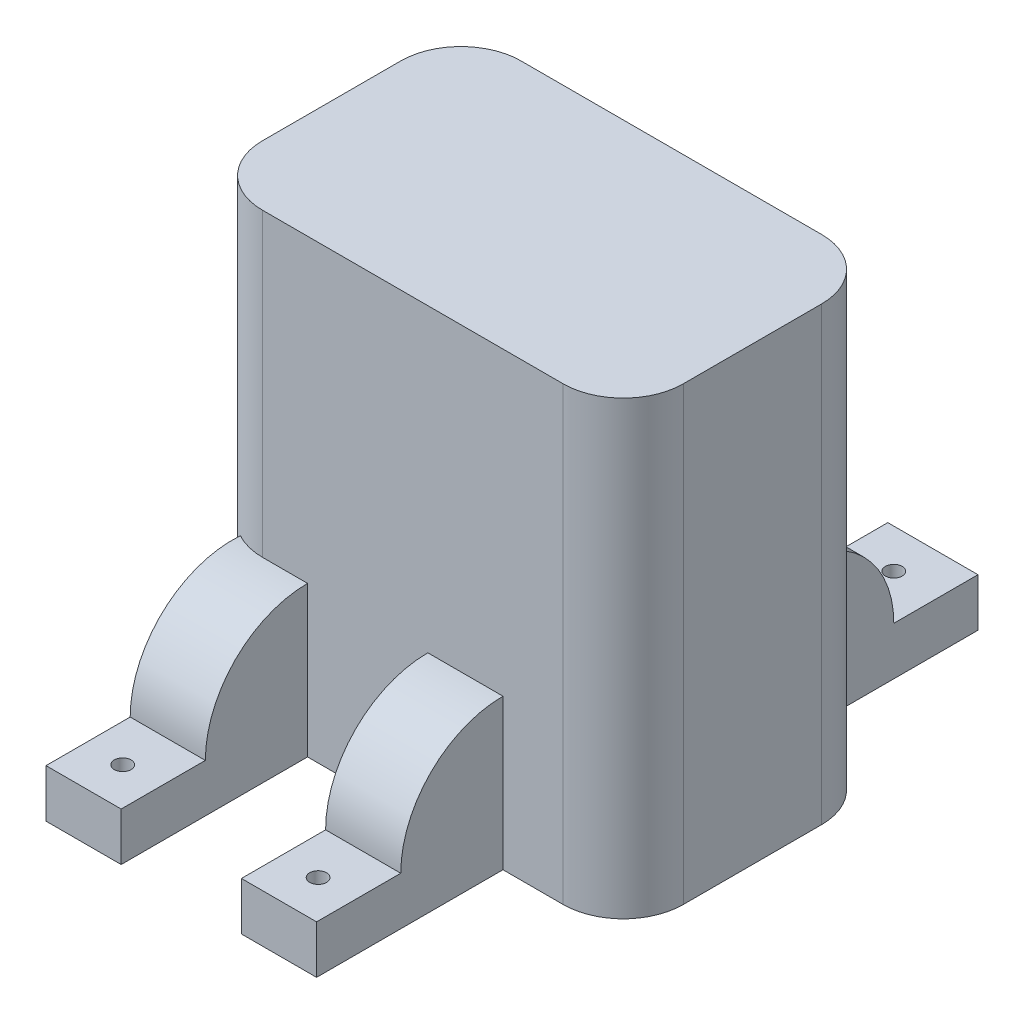
SolidWorks part; units mm, degrees
ref_plane "Plan de face" through (0, 0, 0) normal (0, 0, 1) x (1, 0, 0)
ref_plane "Plan de dessus" through (0, 0, 0) normal (0, 1, 0) x (1, 0, 0)
ref_plane "Plan de droite" through (0, 0, 0) normal (1, 0, 0) x (0, 0, -1)
sketch "Esquisse1" plane through (0, 0, 0) normal (0, 1, 0) x (1, 0, 0)
  line L1 (0, 0) -> (7, 0)
  line L2 (0, 0) -> (0, 4.3)
  line L3 (0, 4.3) -> (7, 4.3)
  line L4 (7, 0) -> (7, 4.3)
  dimension "D1" = 7
  dimension "D2" = 4.3
extrude "Boss.-Extru.1" add sketch "Esquisse1" along normal blind 7.5
shell "Coque1" thickness 1 removed face at (3.5, 0, -2.15)
sketch "Esquisse2" plane through (0, 0, 0) normal (0, 0, 1) x (1, 0, 0)
  line L0 (7, 0) -> (5, 0)
  line L1 (0, 0) -> (7, 0) construction
  line L2 (5, 0) -> (3.75, 0)
  line L3 (3.75, 0) -> (1.75, 0)
  line L4 (1.75, 0) -> (0.5, 0)
  line L5 (0.5, 0) -> (0, 0)
  line L7 (0.5, 0) -> (1.75, 0)
  line L8 (0.5, 0) -> (0.5, 0.8)
  line L9 (0.5, 0.8) -> (1.75, 0.8)
  line L10 (1.75, 0) -> (1.75, 0.8)
  line L11 (3.75, 0) -> (5, 0)
  line L12 (3.75, 0) -> (3.75, 0.8)
  line L13 (3.75, 0.8) -> (5, 0.8)
  line L14 (5, 0) -> (5, 0.8)
  dimension "D1" = 0.5
  dimension "D2" = 2
  dimension "D3" = 2
  dimension "D4" = 0.8
extrude "Boss.-Extru.2" add sketch "Esquisse2" along normal blind 3.1 from surface contours L8 L7 L10 L9 | L12 L11 L14 L13 starting at face at (3.5, 3.75, 0)
sketch "Esquisse3" plane through (0, 0, -4.3) normal (0, 0, -1) x (-1, 0, 0)
  line L0 (-7, 0) -> (-5.5, 0)
  line L1 (-7, 0) -> (0, 0) construction
  line L2 (0, 0) -> (-4, 0)
  line L4 (-5.5, 0) -> (-4, 0)
  line L5 (-5.5, 0) -> (-5.5, 0.8)
  line L6 (-5.5, 0.8) -> (-4, 0.8)
  line L7 (-4, 0) -> (-4, 0.8)
  dimension "D1" = 1.5
  dimension "D2" = 4
  dimension "D3" = 0.8
extrude "Boss.-Extru.3" add sketch "Esquisse3" along normal blind 3.1 from surface contours L5 L4 L7 L6 starting at face at (3.5, 3.75, -4.3)
sketch "Esquisse4" plane through (0, 0.8, 0) normal (0, 1, 0) x (1, 0, 0)
  line L0 (7, 4.3) -> (0, 4.3) construction
  line L3 (5.5, 7.4) -> (5.5, 4.3) construction
  line L4 (0, 0) -> (7, 0) construction
  line L5 (3.75, -3.1) -> (5, -3.1) construction
  line L8 (0.5, -3.1) -> (1.75, -3.1) construction
  circle A0 centre (4.75, 6.75) radius 0.14
  circle A1 centre (1.125, -2.45) radius 0.14
  circle A2 centre (4.375, -2.45) radius 0.14
  point P12 (0, 0)
  point P13 (1.125, -3.1)
  point P19 (4.375, -3.1)
  dimension "D1" = 0.28
  dimension "D2" = 2.45
  dimension "D4" = 0.28
  dimension "D5" = 0.28
  dimension "D3" = 0.75
  dimension "D6" = 2.45
  dimension "D7" = 2.45
extrude "Enlèv. mat.-Extru.1" cut sketch "Esquisse4" against normal through all
sketch "Esquisse5" plane through (5, 0, 0) normal (1, 0, 0) x (0, 0, -1)
  line L3 (-3.1, 0.8) -> (0, 0.8) construction
  line L4 (0, 7.5) -> (0, 0) construction
  line L5 (0, 2.5) -> (0, 0.8)
  line L6 (0, 0.8) -> (-1.7, 0.8)
  arc A2 (-1.7, 0.8) -> (0, 2.5) centre (0, 0.8) cw
  dimension "D1" = 1.7
extrude "Boss.-Extru.4" add sketch "Esquisse5" against normal up to surface (1.25 mm away) up to face at (3.75, 0.4, 1.55)
sketch "Esquisse6" plane through (0.5, 0, 0) normal (-1, 0, 0) x (0, 0, 1)
  line L0 (3.1, 0.8) -> (0, 0.8) construction
  line L1 (0, 7.5) -> (0, 0) construction
  line L2 (0, 2.5) -> (0, 0.8)
  line L3 (0, 0.8) -> (1.7, 0.8)
  arc A0 (1.7, 0.8) -> (0, 2.5) centre (0, 0.8) ccw
  dimension "D1" = 1.7
extrude "Boss.-Extru.5" add sketch "Esquisse6" against normal up to surface (1.25 mm away) up to face at (1.75, 0.4, 1.55)
sketch "Esquisse7" plane through (4, 0, 0) normal (-1, 0, 0) x (0, 0, 1)
  line L0 (-7.4, 0.8) -> (-4.3, 0.8) construction
  line L1 (-4.3, 7.5) -> (-4.3, 0) construction
  line L2 (-4.3, 2.5) -> (-4.3, 0.8)
  line L3 (-4.3, 0.8) -> (-6, 0.8)
  arc A0 (-6, 0.8) -> (-4.3, 2.5) centre (-4.3, 0.8) cw
  dimension "D1" = 1.7
extrude "Boss.-Extru.6" add sketch "Esquisse7" against normal up to surface (1.5 mm away) up to face at (5.5, 0.4, -5.85)
fillet "Congé1" radius 1 4 edges at (0, 3.75, 0) (0, 3.75, -4.3) (7, 3.75, -4.3) (7, 3.75, 0)
